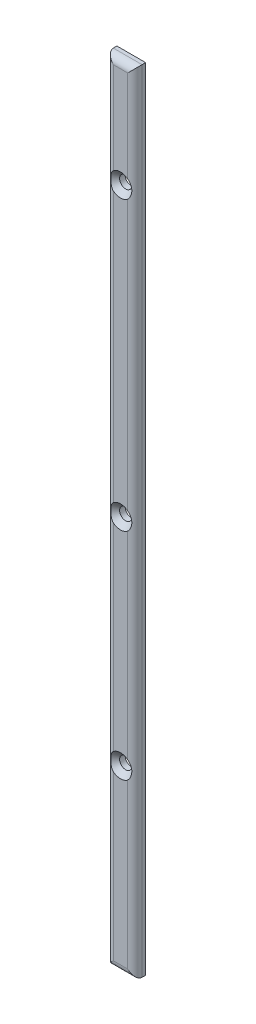
SolidWorks part; units mm, degrees
ref_plane "Front Plane" through (0, 0, 0) normal (0, 0, 1) x (1, 0, 0)
ref_plane "Top Plane" through (0, 0, 0) normal (0, 1, 0) x (1, 0, 0)
ref_plane "Right Plane" through (0, 0, 0) normal (1, 0, 0) x (0, 0, -1)
sketch "ｽｹｯﾁ1" plane through (0, 0, 0) normal (0, 0, 1) x (1, 0, 0)
  line L1 (4, -110) -> (-4, -110)
  line L2 (4, -110) -> (4, 110)
  line L3 (4, 110) -> (-4, 110)
  line L4 (-4, -110) -> (-4, 110)
  line L5 (4, -110) -> (-4, 110) construction
  line L6 (4, 110) -> (-4, -110) construction
  circle A0 centre (0, 80) radius 1.6
  circle A1 centre (0, 0) radius 1.6
  circle A2 centre (0, -60) radius 1.6
  point P0 (0, 0)
  point P12 (0, -110)
  dimension "D1" = 3.2
  dimension "D2" = 3.2
  dimension "D3" = 3.2
  dimension "D5" = 80
  dimension "D7" = 0
  dimension "D8" = 50
  dimension "D4" = 8
  dimension "D6" = 30
extrude "ﾎﾞｽ - 押し出し1" add sketch "ｽｹｯﾁ1" along normal blind 3
hole_wizard "M3 平皿頭ねじ用皿穴1" positions "ｽｹｯﾁ5" profile "ｽｹｯﾁ6" countersink size "M3" standard "JIS"
sketch "ｽｹｯﾁ5" plane through (0, 0, 3) normal (0, 0, 1) x (1, 0, 0)
  point P0 (0, -60)
  point P3 (0, 0)
  point P6 (0, 80)
sketch "ｽｹｯﾁ6" plane through (0, -60, 3) normal (1, 0, 0) x (0, -1, 0)
  line L0 (0, 0) -> (0, 6.0215)
  line L1 (0, 6.0215) -> (1.7, 5)
  line L2 (1.7, 5) -> (1.7, 1.45)
  line L3 (1.7, 1.45) -> (3.15, 0)
  line L5 (3.15, 0) -> (0, 0)
  line L6 (-1.7, 1.45) -> (-3.15, 0) construction
  line L10 (0, 6.0215) -> (-1.7, 5) construction
  line L11 (0, -6.35) -> (0, 107.95) construction
  dimension "穴の直径" = 3.4
  dimension "穴の深さ" = 5
  dimension "表面の皿穴の直径" = 6.3
  dimension "表面の皿穴の角度" = 90
  dimension "ﾄﾞﾘﾙ角度" = 118
fillet "ﾌｨﾚｯﾄ1" radius 2 4 edges at (0, -110, 3) (0, 110, 3) (-4, 0, 3) (4, 0, 3)
